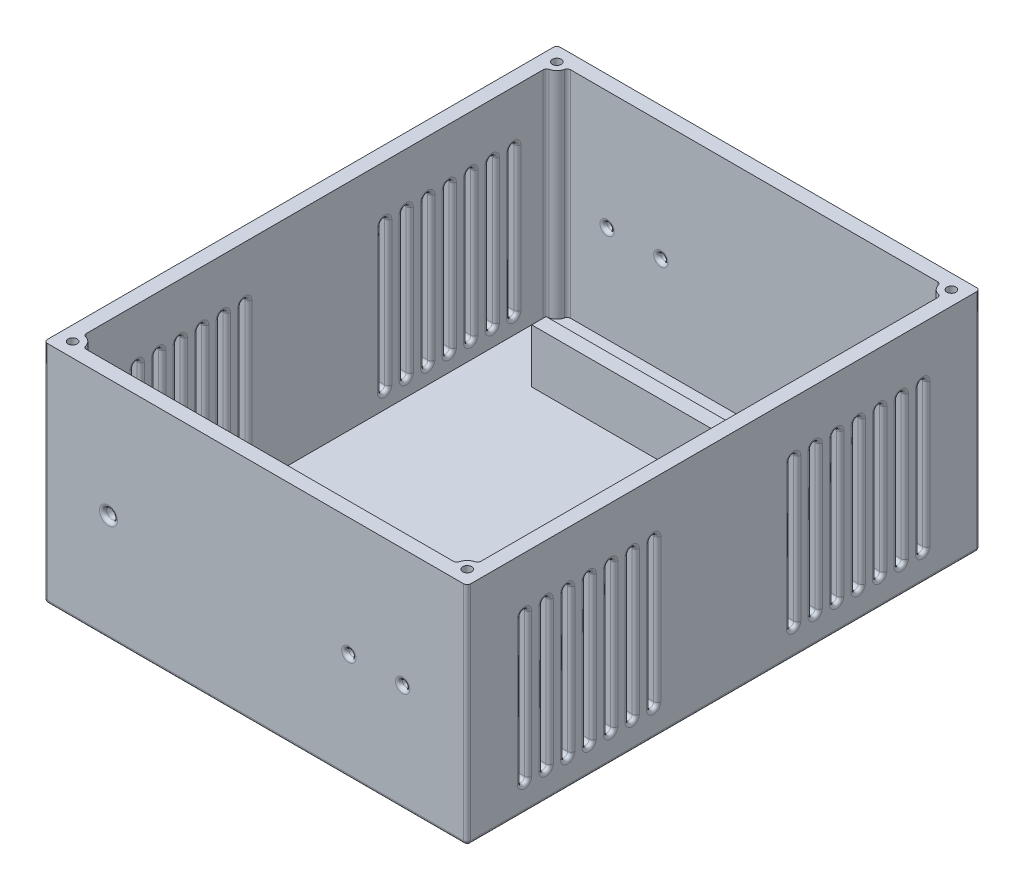
SolidWorks part; units mm, degrees
ref_plane "Front Plane" through (0, 0, 0) normal (0, 0, 1) x (1, 0, 0)
ref_plane "Top Plane" through (0, 0, 0) normal (0, 1, 0) x (1, 0, 0)
ref_plane "Right Plane" through (0, 0, 0) normal (1, 0, 0) x (0, 0, -1)
sketch "Sketch20" plane through (0, 0, 0) normal (0, 1, 0) x (1, 0, 0)
  line L1 (-50, 50) -> (50, 50)
  line L2 (-50, 50) -> (-50, -50)
  line L3 (-50, -50) -> (50, -50)
  line L4 (50, 50) -> (50, -50)
  line L5 (-50, 50) -> (50, -50) construction
  line L6 (-50, -50) -> (50, 50) construction
  line L7 (-55, 67.5) -> (55, 67.5)
  line L8 (-55, 67.5) -> (-55, -67.5)
  line L9 (-55, -67.5) -> (55, -67.5)
  line L10 (55, 67.5) -> (55, -67.5)
  line L11 (-55, 67.5) -> (55, -67.5) construction
  line L12 (-55, -67.5) -> (55, 67.5) construction
  line L13 (-59, 71.5) -> (59, 71.5)
  line L14 (-59, 71.5) -> (-59, -71.5)
  line L15 (-59, -71.5) -> (59, -71.5)
  line L16 (59, 71.5) -> (59, -71.5)
  line L17 (-59, 71.5) -> (59, -71.5) construction
  line L18 (-59, -71.5) -> (59, 71.5) construction
  point P0 (0, 0)
  point P6 (0, 0)
  point P11 (0, 0)
  dimension "D1" = 118
  dimension "D2" = 143
  dimension "D3" = 110
  dimension "D4" = 135
extrude "Boss-Extrude7" add sketch "Sketch20" along normal blind 3 contours L8 L9 L10 L7
extrude "Boss-Extrude8" add sketch "Sketch20<4>" along normal blind 63 contours L14 L15 L16 L13 | L8 L9 L10 L7
sketch "Sketch20<4>" plane through (0, 0, 0) normal (0, 1, 0) x (1, 0, 0) same geometry as "Sketch20"
sketch "Sketch21" plane through (0, 3, 0) normal (0, 1, 0) x (1, 0, 0)
  line L1 (-55, 67.5) -> (-55, -67.5) construction
  line L2 (-55, -67.5) -> (55, -67.5) construction
  line L3 (-55, -67.5) -> (-55, -64.5)
  line L4 (-55, -67.5) -> (-52, -67.5)
  line L5 (-55, 0) -> (55, 0) construction
  line L6 (55, 67.5) -> (55, -67.5) construction
  line L7 (0, 67.5) -> (0, -67.5) construction
  line L8 (-55, 67.5) -> (55, 67.5) construction
  line L9 (-55, 67.5) -> (-52, 67.5)
  line L10 (-55, 67.5) -> (-55, 64.5)
  line L11 (55, -67.5) -> (52, -67.5)
  line L12 (55, -67.5) -> (55, -64.5)
  line L13 (55, 67.5) -> (55, 64.5)
  line L14 (55, 67.5) -> (52, 67.5)
  arc A0 (-55, -64.5) -> (-52, -67.5) centre (-55, -67.5) cw
  arc A1 (-55, 64.5) -> (-52, 67.5) centre (-55, 67.5) ccw
  arc A2 (55, -64.5) -> (52, -67.5) centre (55, -67.5) ccw
  arc A3 (55, 64.5) -> (52, 67.5) centre (55, 67.5) cw
extrude "Boss-Extrude9" add sketch "Sketch21" along normal blind 60
sketch "Sketch22" plane through (0, 63, 0) normal (0, 1, 0) x (1, 0, 0)
  circle A0 centre (-55, -67.5) radius 1.25
  circle A1 centre (-55, 67.5) radius 1.25
  circle A2 centre (55, 67.5) radius 1.25
  circle A3 centre (55, -67.5) radius 1.25
extrude "Cut-Extrude9" cut sketch "Sketch22" against normal blind 40
fillet "Fillet1" radius 1 8 edges at (-52, 33, -67.5) (-55, 33, -64.5) (-55, 33, 64.5) (52, 33, 67.5) (55, 33, 64.5) (55, 33, -64.5) (52, 33, -67.5) (-52, 33, 67.5)
sketch "Sketch27" plane through (0, 0, -71.5) normal (0, 0, -1) x (-1, 0, 0)
  line L0 (59, 0) -> (-59, 0) construction
  line L3 (-59, 63) -> (-59, 0) construction
  line L4 (0, 63) -> (0, 0) construction
  line L5 (59, 63) -> (-59, 63) construction
  circle A0 centre (-41, 30) radius 1
  circle A1 centre (-26, 30) radius 1
  circle A2 centre (41, 30) radius 1
  circle A3 centre (26, 30) radius 1
  dimension "D1" = 30
  dimension "D3" = 2
  dimension "D4" = 15
  dimension "D2" = 18
extrude "Cut-Extrude7" cut sketch "Sketch27" against normal blind 4
sketch "Sketch28" plane through (0, 0, 71.5) normal (0, 0, 1) x (1, 0, 0)
  line L0 (-59, 0) -> (59, 0) construction
  line L1 (-59, 63) -> (-59, 0) construction
  line L2 (59, 63) -> (59, 0) construction
  circle A0 centre (-41, 30) radius 1.5
  circle A1 centre (41, 30) radius 1
  circle A2 centre (26, 30) radius 1
  dimension "D1" = 30
  dimension "D3" = 18
  dimension "D2" = 18
  dimension "D4" = 15
extrude "Cut-Extrude8" cut sketch "Sketch28" against normal blind 4
sketch "Sketch29" plane through (0, 3, 0) normal (0, 1, 0) x (1, 0, 0)
  line L0 (-51.127, 67.5) -> (51.127, 67.5) construction
  line L5 (-51.127, -67.5) -> (51.127, -67.5) construction
  line L12 (40, 49.5) -> (-40, 49.5)
  line L17 (40, 49.5) -> (40, 45.5)
  line L18 (40, 45.5) -> (-40, 45.5)
  line L20 (-40, 49.5) -> (-40, 45.5)
  line L21 (40, 49.5) -> (-40, 45.5) construction
  line L22 (40, 45.5) -> (-40, 49.5) construction
  line L23 (40, -49.5) -> (-40, -49.5)
  line L24 (40, -49.5) -> (40, -45.5)
  line L25 (40, -45.5) -> (-40, -45.5)
  line L26 (-40, -49.5) -> (-40, -45.5)
  line L27 (40, -49.5) -> (-40, -45.5) construction
  line L28 (40, -45.5) -> (-40, -49.5) construction
  point P0 (0, 0)
  point P1 (-40, 47.5)
  point P4 (-40, -47.5)
  point P6 (0, 47.5)
  point P10 (-46.2915, 0)
  point P12 (0, -47.5)
  point P15 (46.2915, 0)
  point P18 (0, 0)
  dimension "D1" = 20
  dimension "D2" = 20
extrude "Boss-Extrude11" add sketch "Sketch29" along normal blind 15
fillet "Fillet3" radius 1 14 edges at (27, 30, 71.5) (42, 30, 71.5) (-39.5, 30, 71.5) (27, 30, 67.5) (42, 30, 67.5) (-39.5, 30, 67.5) (-40, 30, -67.5) (-25, 30, -67.5) (40, 30, -67.5) (25, 30, -67.5) (25, 30, -71.5) (-40, 30, -71.5) (-25, 30, -71.5) (40, 30, -71.5)
sketch "Sketch31" plane through (59, 0, 0) normal (1, 0, 0) x (0, 0, -1)
  line L0 (-55.5, 48) -> (-55.5, 8) construction
  line L1 (-54.5, 48) -> (-54.5, 8)
  line L2 (-56.5, 48) -> (-56.5, 8)
  line L3 (-49.5, 48) -> (-49.5, 8) construction
  line L4 (-48.5, 48) -> (-48.5, 8)
  line L5 (-50.5, 48) -> (-50.5, 8)
  line L6 (-43.5, 48) -> (-43.5, 8) construction
  line L7 (-42.5, 48) -> (-42.5, 8)
  line L8 (-44.5, 48) -> (-44.5, 8)
  line L9 (-37.5, 48) -> (-37.5, 8) construction
  line L10 (-36.5, 48) -> (-36.5, 8)
  line L11 (-38.5, 48) -> (-38.5, 8)
  line L12 (-31.5, 48) -> (-31.5, 8) construction
  line L13 (-30.5, 48) -> (-30.5, 8)
  line L14 (-32.5, 48) -> (-32.5, 8)
  line L15 (-25.5, 48) -> (-25.5, 8) construction
  line L16 (-24.5, 48) -> (-24.5, 8)
  line L17 (-26.5, 48) -> (-26.5, 8)
  line L18 (-19.5, 48) -> (-19.5, 8) construction
  line L19 (-18.5, 48) -> (-18.5, 8)
  line L20 (-20.5, 48) -> (-20.5, 8)
  line L22 (71.5, 0) -> (-71.5, 0) construction
  line L23 (-71.5, 63) -> (-71.5, 0) construction
  line L24 (0, 63) -> (0, 0) construction
  line L25 (71.5, 63) -> (-71.5, 63) construction
  line L26 (19.5, 48) -> (19.5, 8) construction
  line L27 (18.5, 48) -> (18.5, 8)
  line L28 (20.5, 48) -> (20.5, 8)
  line L29 (25.5, 48) -> (25.5, 8) construction
  line L30 (24.5, 48) -> (24.5, 8)
  line L31 (26.5, 48) -> (26.5, 8)
  line L32 (31.5, 48) -> (31.5, 8) construction
  line L33 (30.5, 48) -> (30.5, 8)
  line L34 (32.5, 48) -> (32.5, 8)
  line L35 (37.5, 48) -> (37.5, 8) construction
  line L36 (36.5, 48) -> (36.5, 8)
  line L37 (38.5, 48) -> (38.5, 8)
  line L38 (43.5, 48) -> (43.5, 8) construction
  line L39 (42.5, 48) -> (42.5, 8)
  line L40 (44.5, 48) -> (44.5, 8)
  line L41 (49.5, 48) -> (49.5, 8) construction
  line L42 (48.5, 48) -> (48.5, 8)
  line L43 (50.5, 48) -> (50.5, 8)
  line L44 (55.5, 48) -> (55.5, 8) construction
  line L45 (54.5, 48) -> (54.5, 8)
  line L46 (56.5, 48) -> (56.5, 8)
  arc A0 (-54.5, 48) -> (-56.5, 48) centre (-55.5, 48) ccw
  arc A1 (-56.5, 8) -> (-54.5, 8) centre (-55.5, 8) ccw
  arc A2 (-48.5, 48) -> (-50.5, 48) centre (-49.5, 48) ccw
  arc A3 (-50.5, 8) -> (-48.5, 8) centre (-49.5, 8) ccw
  arc A4 (-42.5, 48) -> (-44.5, 48) centre (-43.5, 48) ccw
  arc A5 (-44.5, 8) -> (-42.5, 8) centre (-43.5, 8) ccw
  arc A6 (-36.5, 48) -> (-38.5, 48) centre (-37.5, 48) ccw
  arc A7 (-38.5, 8) -> (-36.5, 8) centre (-37.5, 8) ccw
  arc A8 (-30.5, 48) -> (-32.5, 48) centre (-31.5, 48) ccw
  arc A9 (-32.5, 8) -> (-30.5, 8) centre (-31.5, 8) ccw
  arc A10 (-24.5, 48) -> (-26.5, 48) centre (-25.5, 48) ccw
  arc A11 (-26.5, 8) -> (-24.5, 8) centre (-25.5, 8) ccw
  arc A12 (-18.5, 48) -> (-20.5, 48) centre (-19.5, 48) ccw
  arc A13 (-20.5, 8) -> (-18.5, 8) centre (-19.5, 8) ccw
  arc A14 (18.5, 48) -> (20.5, 48) centre (19.5, 48) cw
  arc A15 (20.5, 8) -> (18.5, 8) centre (19.5, 8) cw
  arc A16 (24.5, 48) -> (26.5, 48) centre (25.5, 48) cw
  arc A17 (26.5, 8) -> (24.5, 8) centre (25.5, 8) cw
  arc A18 (30.5, 48) -> (32.5, 48) centre (31.5, 48) cw
  arc A19 (32.5, 8) -> (30.5, 8) centre (31.5, 8) cw
  arc A20 (36.5, 48) -> (38.5, 48) centre (37.5, 48) cw
  arc A21 (38.5, 8) -> (36.5, 8) centre (37.5, 8) cw
  arc A22 (42.5, 48) -> (44.5, 48) centre (43.5, 48) cw
  arc A23 (44.5, 8) -> (42.5, 8) centre (43.5, 8) cw
  arc A24 (48.5, 48) -> (50.5, 48) centre (49.5, 48) cw
  arc A25 (50.5, 8) -> (48.5, 8) centre (49.5, 8) cw
  arc A26 (54.5, 48) -> (56.5, 48) centre (55.5, 48) cw
  arc A27 (56.5, 8) -> (54.5, 8) centre (55.5, 8) cw
  point P2 (-55.5, 28)
  point P9 (-49.5, 28)
  point P16 (-43.5, 28)
  point P23 (-37.5, 28)
  point P30 (-31.5, 28)
  point P37 (-25.5, 28)
  point P44 (-19.5, 28)
  point P51 (19.5, 28)
  point P66 (25.5, 28)
  point P73 (31.5, 28)
  point P80 (37.5, 28)
  point P87 (43.5, 28)
  point P94 (49.5, 28)
  point P101 (55.5, 28)
  dimension "D1" = 11
  dimension "D2" = 6
  dimension "D3" = 6
  dimension "D4" = 6
  dimension "D5" = 6
  dimension "D6" = 6
  dimension "D7" = 6
  dimension "D8" = 8
  dimension "D9" = 15
sketch "Sketch32" plane through (-59, 0, 0) normal (-1, 0, 0) x (0, 0, 1)
  line L0 (-55.5, 48) -> (-55.5, 8) construction
  line L1 (-54.5, 48) -> (-54.5, 8)
  line L2 (-56.5, 48) -> (-56.5, 8)
  line L3 (-49.5, 48) -> (-49.5, 8) construction
  line L4 (-48.5, 48) -> (-48.5, 8)
  line L5 (-50.5, 48) -> (-50.5, 8)
  line L6 (-43.5, 48) -> (-43.5, 8) construction
  line L7 (-42.5, 48) -> (-42.5, 8)
  line L8 (-44.5, 48) -> (-44.5, 8)
  line L9 (-37.5, 48) -> (-37.5, 8) construction
  line L10 (-36.5, 48) -> (-36.5, 8)
  line L11 (-38.5, 48) -> (-38.5, 8)
  line L12 (-31.5, 48) -> (-31.5, 8) construction
  line L13 (-30.5, 48) -> (-30.5, 8)
  line L14 (-32.5, 48) -> (-32.5, 8)
  line L15 (-25.5, 48) -> (-25.5, 8) construction
  line L16 (-24.5, 48) -> (-24.5, 8)
  line L17 (-26.5, 48) -> (-26.5, 8)
  line L18 (-19.5, 48) -> (-19.5, 8) construction
  line L19 (-18.5, 48) -> (-18.5, 8)
  line L20 (-20.5, 48) -> (-20.5, 8)
  line L21 (0, 63) -> (0, 0) construction
  line L25 (-71.5, 0) -> (71.5, 0) construction
  line L26 (-71.5, 63) -> (-71.5, 0) construction
  line L27 (-71.5, 63) -> (71.5, 63) construction
  line L28 (19.5, 48) -> (19.5, 8) construction
  line L29 (18.5, 48) -> (18.5, 8)
  line L30 (20.5, 48) -> (20.5, 8)
  line L31 (25.5, 48) -> (25.5, 8) construction
  line L32 (24.5, 48) -> (24.5, 8)
  line L33 (26.5, 48) -> (26.5, 8)
  line L34 (31.5, 48) -> (31.5, 8) construction
  line L35 (30.5, 48) -> (30.5, 8)
  line L36 (32.5, 48) -> (32.5, 8)
  line L37 (37.5, 48) -> (37.5, 8) construction
  line L38 (36.5, 48) -> (36.5, 8)
  line L39 (38.5, 48) -> (38.5, 8)
  line L40 (43.5, 48) -> (43.5, 8) construction
  line L41 (42.5, 48) -> (42.5, 8)
  line L42 (44.5, 48) -> (44.5, 8)
  line L43 (49.5, 48) -> (49.5, 8) construction
  line L44 (48.5, 48) -> (48.5, 8)
  line L45 (50.5, 48) -> (50.5, 8)
  line L46 (55.5, 48) -> (55.5, 8) construction
  line L47 (54.5, 48) -> (54.5, 8)
  line L48 (56.5, 48) -> (56.5, 8)
  arc A0 (-54.5, 48) -> (-56.5, 48) centre (-55.5, 48) ccw
  arc A1 (-56.5, 8) -> (-54.5, 8) centre (-55.5, 8) ccw
  arc A2 (-48.5, 48) -> (-50.5, 48) centre (-49.5, 48) ccw
  arc A3 (-50.5, 8) -> (-48.5, 8) centre (-49.5, 8) ccw
  arc A4 (-42.5, 48) -> (-44.5, 48) centre (-43.5, 48) ccw
  arc A5 (-44.5, 8) -> (-42.5, 8) centre (-43.5, 8) ccw
  arc A6 (-36.5, 48) -> (-38.5, 48) centre (-37.5, 48) ccw
  arc A7 (-38.5, 8) -> (-36.5, 8) centre (-37.5, 8) ccw
  arc A8 (-30.5, 48) -> (-32.5, 48) centre (-31.5, 48) ccw
  arc A9 (-32.5, 8) -> (-30.5, 8) centre (-31.5, 8) ccw
  arc A10 (-24.5, 48) -> (-26.5, 48) centre (-25.5, 48) ccw
  arc A11 (-26.5, 8) -> (-24.5, 8) centre (-25.5, 8) ccw
  arc A12 (-18.5, 48) -> (-20.5, 48) centre (-19.5, 48) ccw
  arc A13 (-20.5, 8) -> (-18.5, 8) centre (-19.5, 8) ccw
  arc A16 (18.5, 48) -> (20.5, 48) centre (19.5, 48) cw
  arc A17 (20.5, 8) -> (18.5, 8) centre (19.5, 8) cw
  arc A18 (24.5, 48) -> (26.5, 48) centre (25.5, 48) cw
  arc A19 (26.5, 8) -> (24.5, 8) centre (25.5, 8) cw
  arc A20 (30.5, 48) -> (32.5, 48) centre (31.5, 48) cw
  arc A21 (32.5, 8) -> (30.5, 8) centre (31.5, 8) cw
  arc A22 (36.5, 48) -> (38.5, 48) centre (37.5, 48) cw
  arc A23 (38.5, 8) -> (36.5, 8) centre (37.5, 8) cw
  arc A24 (42.5, 48) -> (44.5, 48) centre (43.5, 48) cw
  arc A25 (44.5, 8) -> (42.5, 8) centre (43.5, 8) cw
  arc A26 (48.5, 48) -> (50.5, 48) centre (49.5, 48) cw
  arc A27 (50.5, 8) -> (48.5, 8) centre (49.5, 8) cw
  arc A28 (54.5, 48) -> (56.5, 48) centre (55.5, 48) cw
  arc A29 (56.5, 8) -> (54.5, 8) centre (55.5, 8) cw
  point P2 (-55.5, 28)
  point P9 (-49.5, 28)
  point P16 (-43.5, 28)
  point P23 (-37.5, 28)
  point P30 (-31.5, 28)
  point P37 (-25.5, 28)
  point P44 (-19.5, 28)
  point P55 (19.5, 28)
  point P66 (25.5, 28)
  point P73 (31.5, 28)
  point P80 (37.5, 28)
  point P87 (43.5, 28)
  point P94 (49.5, 28)
  point P101 (55.5, 28)
  dimension "D1" = 6
  dimension "D2" = 6
  dimension "D3" = 6
  dimension "D4" = 6
  dimension "D5" = 6
  dimension "D6" = 6
  dimension "D8" = 8
  dimension "D9" = 15
extrude "Cut-Extrude10" cut sketch "Sketch31" against normal blind 4
extrude "Cut-Extrude11" cut sketch "Sketch32" against normal blind 4
fillet "Fillet5" radius 1 232 edges at (-59, 0, 0) (-59, 31.5, -71.5) (0, 0, -71.5) (59, 31.5, -71.5) (59, 0, 0) (59, 31.5, 71.5) (-59, 31.5, 71.5) (0, 0, 71.5) (-55, 28, 56.5) (-55, 7, 55.5) (-55, 28, 54.5) (-55, 49, 55.5) (-55, 28, 50.5) (-55, 7, 49.5) (-55, 28, 48.5) (-55, 49, 49.5) (-55, 28, 44.5) (-55, 7, 43.5) (-55, 28, 42.5) (-55, 49, 43.5) (-55, 28, 38.5) (-55, 7, 37.5) (-55, 28, 36.5) (-55, 49, 37.5) (-55, 28, 32.5) (-55, 7, 31.5) (-55, 28, 30.5) (-55, 49, 31.5) (-55, 28, 26.5) (-55, 7, 25.5) (-55, 28, 24.5) (-55, 49, 25.5) (-55, 28, 20.5) (-55, 7, 19.5) (-55, 49, 19.5) (-55, 28, -18.5) (-55, 7, -19.5) (-55, 28, -20.5) (-55, 49, -19.5) (-55, 28, -24.5) (-55, 7, -25.5) (-55, 28, -26.5) (-55, 49, -25.5) (-55, 28, -30.5) (-55, 7, -31.5) (-55, 28, -32.5) (-55, 49, -31.5) (-55, 28, -36.5) (-55, 7, -37.5) (-55, 28, -38.5) (-55, 49, -37.5) (-55, 28, -42.5) (-55, 7, -43.5) (-55, 28, -44.5) (-55, 49, -43.5) (-55, 28, -48.5) (-55, 7, -49.5) (-55, 28, -50.5) (-55, 49, -49.5) (-55, 28, -54.5) (-55, 7, -55.5) (-55, 28, -56.5) (-55, 49, -55.5) (-55, 28, 18.5) (-59, 7, 55.5) (-59, 28, 56.5) (-59, 49, 55.5) (-59, 28, 54.5) (-59, 7, 49.5) (-59, 28, 50.5) (-59, 49, 49.5) (-59, 28, 48.5) (-59, 7, 43.5) (-59, 28, 44.5) (-59, 49, 43.5) (-59, 28, 42.5) (-59, 7, 37.5) (-59, 28, 38.5) (-59, 49, 37.5) (-59, 28, 36.5) (-59, 7, 31.5) (-59, 28, 32.5) (-59, 49, 31.5) (-59, 28, 30.5) (-59, 7, 25.5) (-59, 28, 26.5) (-59, 49, 25.5) (-59, 28, 24.5) (-59, 7, 19.5) (-59, 28, 20.5) (-59, 49, 19.5) (-59, 7, -19.5) (-59, 28, -18.5) (-59, 49, -19.5) (-59, 28, -20.5) (-59, 7, -25.5) (-59, 28, -24.5) (-59, 49, -25.5) (-59, 28, -26.5) (-59, 7, -31.5) (-59, 28, -30.5) (-59, 49, -31.5) (-59, 28, -32.5) (-59, 7, -37.5) (-59, 28, -36.5) (-59, 49, -37.5) (-59, 28, -38.5) (-59, 7, -43.5) (-59, 28, -42.5) (-59, 49, -43.5) (-59, 28, -44.5) (-59, 7, -49.5) (-59, 28, -48.5) (-59, 49, -49.5) (-59, 28, -50.5) (-59, 7, -55.5) (-59, 28, -54.5) (-59, 49, -55.5) (-59, 28, -56.5) (-59, 28, 18.5) (55, 7, -55.5) (55, 28, -54.5) (55, 49, -55.5) (55, 28, -56.5) (55, 7, -49.5) (55, 28, -48.5) (55, 49, -49.5) (55, 28, -50.5) (55, 7, -43.5) (55, 28, -42.5) (55, 49, -43.5) (55, 28, -44.5) (55, 7, -37.5) (55, 28, -36.5) (55, 49, -37.5) (55, 28, -38.5) (55, 7, -31.5) (55, 28, -30.5) (55, 49, -31.5) (55, 28, -32.5) (55, 7, -25.5) (55, 28, -24.5) (55, 49, -25.5) (55, 28, -26.5) (55, 7, -19.5) (55, 28, -18.5) (55, 49, -19.5) (55, 28, -20.5) (55, 7, 19.5) (55, 28, 20.5) (55, 49, 19.5) (55, 7, 25.5) (55, 28, 26.5) (55, 49, 25.5) (55, 28, 24.5) (55, 7, 31.5) (55, 28, 32.5) (55, 49, 31.5) (55, 28, 30.5) (55, 7, 37.5) (55, 28, 38.5) (55, 49, 37.5) (55, 28, 36.5) (55, 7, 43.5) (55, 28, 44.5) (55, 49, 43.5) (55, 28, 42.5) (55, 7, 49.5) (55, 28, 50.5) (55, 49, 49.5) (55, 28, 48.5) (55, 7, 55.5) (55, 28, 56.5) (55, 49, 55.5) (55, 28, 54.5) (55, 28, 18.5) (59, 28, -54.5) (59, 7, -55.5) (59, 28, -56.5) (59, 49, -55.5) (59, 28, -48.5) (59, 7, -49.5) (59, 28, -50.5) (59, 49, -49.5) (59, 28, -42.5) (59, 7, -43.5) (59, 28, -44.5) (59, 49, -43.5) (59, 28, -36.5) (59, 7, -37.5) (59, 28, -38.5) (59, 49, -37.5) (59, 28, -30.5) (59, 7, -31.5) (59, 28, -32.5) (59, 49, -31.5) (59, 28, -24.5) (59, 7, -25.5) (59, 28, -26.5) (59, 49, -25.5) (59, 28, -18.5) (59, 7, -19.5) (59, 28, -20.5) (59, 49, -19.5) (59, 28, 20.5) (59, 7, 19.5) (59, 28, 18.5) (59, 49, 19.5) (59, 28, 26.5) (59, 7, 25.5) (59, 28, 24.5) (59, 49, 25.5) (59, 28, 32.5) (59, 7, 31.5) (59, 28, 30.5) (59, 49, 31.5) (59, 28, 38.5) (59, 7, 37.5) (59, 28, 36.5) (59, 49, 37.5) (59, 28, 44.5) (59, 7, 43.5) (59, 28, 42.5) (59, 49, 43.5) (59, 28, 50.5) (59, 7, 49.5) (59, 28, 48.5) (59, 49, 49.5) (59, 7, 55.5) (59, 28, 54.5) (59, 49, 55.5) (59, 28, 56.5)
